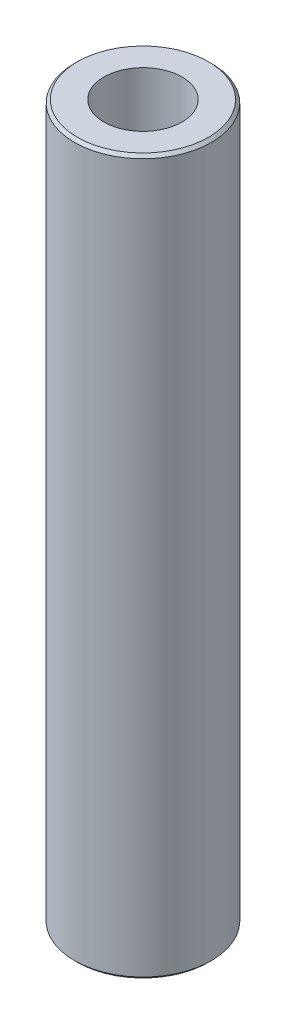
SolidWorks part; units mm, degrees
ref_plane "Front Plane" through (0, 0, 0) normal (0, 0, 1) x (1, 0, 0)
ref_plane "Top Plane" through (0, 0, 0) normal (0, 1, 0) x (1, 0, 0)
ref_plane "Right Plane" through (0, 0, 0) normal (1, 0, 0) x (0, 0, -1)
sketch "Sketch1" plane through (0, 0, 0) normal (0, 1, 0) x (1, 0, 0)
  circle A0 centre (0, 0) radius 57.5
  dimension "SHAFT_OD" = 115
extrude "Boss-Extrude1" add sketch "Sketch1" along normal blind 600
sketch "Sketch2" plane through (0, 0, 0) normal (0, 1, 0) x (1, 0, 0)
  circle A0 centre (0, 0) radius 32.8025
  dimension "BORE_D" = 65.605
extrude "Cut-Extrude1" cut sketch "Sketch2" along normal through all
chamfer "Chamfer1" distance 2.4748 angle 45 2 edges at (0, 600, 57.5) (0, 0, 57.5)
